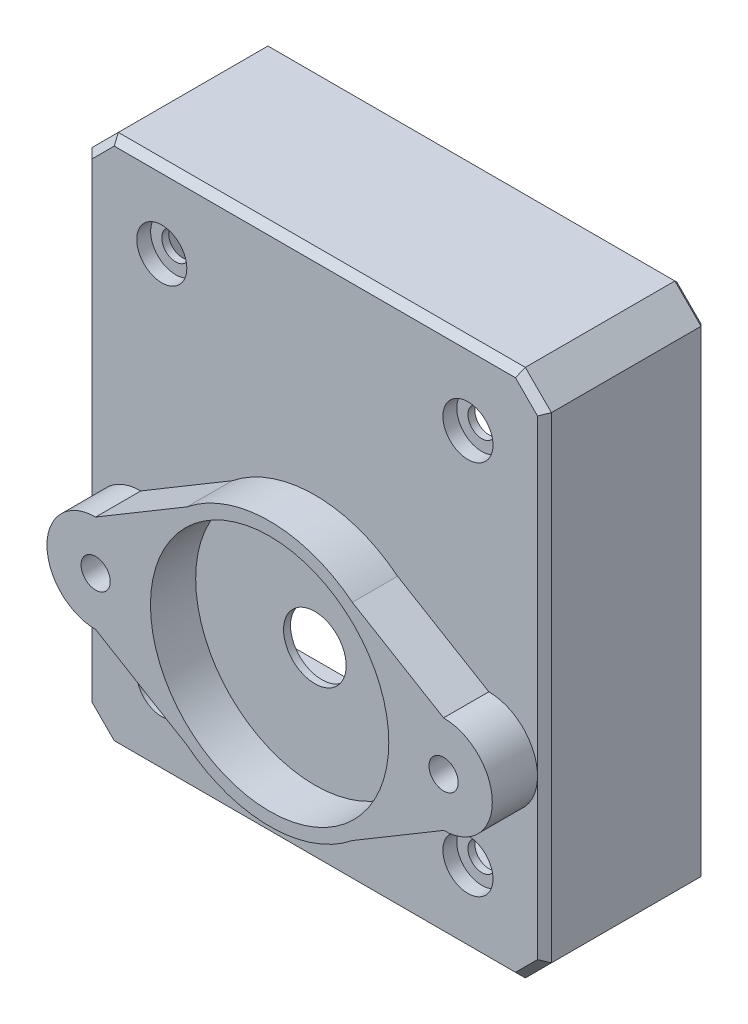
SolidWorks part; units mm, degrees
ref_plane "Ebene vorne" through (0, 0, 0) normal (0, 0, 1) x (1, 0, 0)
ref_plane "Ebene oben" through (0, 0, 0) normal (0, 1, 0) x (1, 0, 0)
ref_plane "Ebene rechts" through (0, 0, 0) normal (1, 0, 0) x (0, 0, -1)
sketch "Skizze1" plane through (0, 0, 0) normal (0, 0, 1) x (1, 0, 0)
  line L1 (0, 0) -> (60, 0)
  line L2 (0, 0) -> (0, 70)
  line L3 (0, 70) -> (60, 70)
  line L4 (60, 0) -> (60, 70)
  dimension "D1" = 60
  dimension "D2" = 70
extrude "Grundkörper" add sketch "Skizze1" along normal blind 20
chamfer "Fase1" distance 2 angle 45 4 edges at (60, 0, 10) (0, 0, 10) (0, 70, 10) (60, 70, 10)
shell "Wandung1" thickness 3 removed face at (30, 35, 0) outward yes
sketch "Skizze2" plane through (0, 0, 23) normal (0, 0, 1) x (1, 0, 0)
  line L0 (2, 0) -> (58, 0) construction
  line L2 (60, 24) -> (30, 24) construction
  line L3 (30, 24) -> (0, 24) construction
  line L4 (60, 2) -> (60, 68) construction
  line L5 (0, 68) -> (0, 2) construction
  circle A0 centre (30, 24) radius 4.5
  dimension "D1" = 9
  dimension "D2" = 24
extrude "Durchbruch Servo" cut sketch "Skizze2" against normal through all
sketch "Skizze4" plane through (0, 0, 20) normal (0, 0, -1) x (-1, 0, 0)
  line L0 (-30, 24) -> (-30, 14) construction
  line L5 (-41, 56) -> (-19, 56)
  line L6 (-41, 56) -> (-41, 14)
  line L7 (-41, 14) -> (-19, 14)
  line L8 (-19, 56) -> (-19, 14)
  dimension "D1" = 42
  dimension "D2" = 22
  dimension "D3" = 10
extrude "ServoFreischnitt" cut sketch "Skizze4" against normal offset from surface (2 mm away) 1 up to face at (34.5, 24, 23)
sketch "Skizze3" plane through (0, 0, 23) normal (0, 0, 1) x (1, 0, 0)
  line L17 (30, 24) -> (30, 9.1792) construction
  line L18 (30, 9.1792) -> (30, 46.6296) construction
  line L20 (30, 24) -> (6.2908, 24) construction
  line L21 (6.2908, 24) -> (30, 24) construction
  line L25 (5, 31) -> (18.1112, 38.8208)
  line L27 (41.8888, 38.8208) -> (55, 31)
  line L31 (41.8888, 9.1792) -> (55, 17)
  line L33 (5, 17) -> (18.1112, 9.1792)
  arc A25 (5, 31) -> (5, 17) centre (5, 24) ccw
  arc A27 (55, 17) -> (55, 31) centre (55, 24) ccw
  arc A30 (18.1112, 9.1792) -> (41.8888, 9.1792) centre (30, 24) ccw
  arc A31 (41.8888, 38.8208) -> (18.1112, 38.8208) centre (30, 24) ccw
  circle A32 centre (5, 24) radius 2.1
  circle A33 centre (55, 24) radius 2.1
  dimension "D3" = 50
  dimension "D1" = 14
  dimension "D2" = 14
  dimension "D5" = 38
  dimension "D6" = 4.2
  dimension "D7" = 4.2
  dimension "D4" = 25
extrude "FlanschAufsatz" add sketch "Skizze3" along normal blind 6.5
sketch "Skizze6" plane through (0, 0, 29.5) normal (0, 0, 1) x (1, 0, 0)
  line L0 (5, 24) -> (55, 24) construction
  line L1 (55, 24) -> (30, 24) construction
  line L2 (30, 24) -> (30, 43) construction
  line L3 (30, 43) -> (30, 5) construction
  arc A0 (41.8888, 38.8208) -> (18.1112, 38.8208) centre (30, 24) ccw construction
  arc A1 (18.1112, 9.1792) -> (41.8888, 9.1792) centre (30, 24) ccw construction
  circle A2 centre (30, 24) radius 17.125
  dimension "D1" = 34.25
extrude "BohrungSchnecke" cut sketch "Skizze6" against normal blind 6.5
sketch "Skizze7" plane through (0, 0, 23) normal (0, 0, 1) x (1, 0, 0)
  line L0 (30, 73) -> (30, -3) construction
  line L1 (59.2426, 73) -> (0.7574, 73) construction
  line L2 (0.7574, -3) -> (59.2426, -3) construction
  line L4 (-3, 69.2426) -> (-3, 0.7574) construction
  line L5 (-3, 35) -> (63, 35) construction
  line L6 (63, 0.7574) -> (63, 69.2426) construction
  circle A0 centre (8, 62) radius 2
  circle A1 centre (52, 62) radius 2
  circle A2 centre (52, 8) radius 2
  circle A3 centre (8, 8) radius 2
  dimension "D1" = 4
  dimension "D2" = 11
  dimension "D3" = 11
extrude "Schnitt-Linear austragen2" cut sketch "Skizze7" against normal up to next
sketch "Skizze8" plane through (0, 0, 23) normal (0, 0, 1) x (1, 0, 0)
  circle A0 centre (8, 62) radius 3.6
  circle A1 centre (52, 62) radius 3.6
  circle A2 centre (52, 8) radius 3.6
  circle A3 centre (8, 8) radius 3.6
  dimension "D1" = 7.2
  dimension "D2" = 7.2
  dimension "D3" = 7.2
  dimension "D4" = 7.2
extrude "Schnitt-Linear austragen3" cut sketch "Skizze8" against normal blind 2
chamfer "Fase2" distance 1 angle 45 8 edges at (61.1213, -1.1213, 23) (63, 35, 23) (61.1213, 71.1213, 23) (30, 73, 23) (-1.1213, 71.1213, 23) (-3, 35, 23) (-1.1213, -1.1213, 23) (30, -3, 23)
chamfer "Fase3" distance 0.5 angle 45 16 edges at (30, 0, 0) (1, 1, 0) (0, 35, 0) (1, 69, 0) (30, 70, 0) (59, 69, 0) (60, 35, 0) (59, 1, 0) (61.1213, 71.1213, 0) (30, 73, 0) (-1.1213, 71.1213, 0) (-3, 35, 0) (-1.1213, -1.1213, 0) (30, -3, 0) (61.1213, -1.1213, 0) (63, 35, 0)
